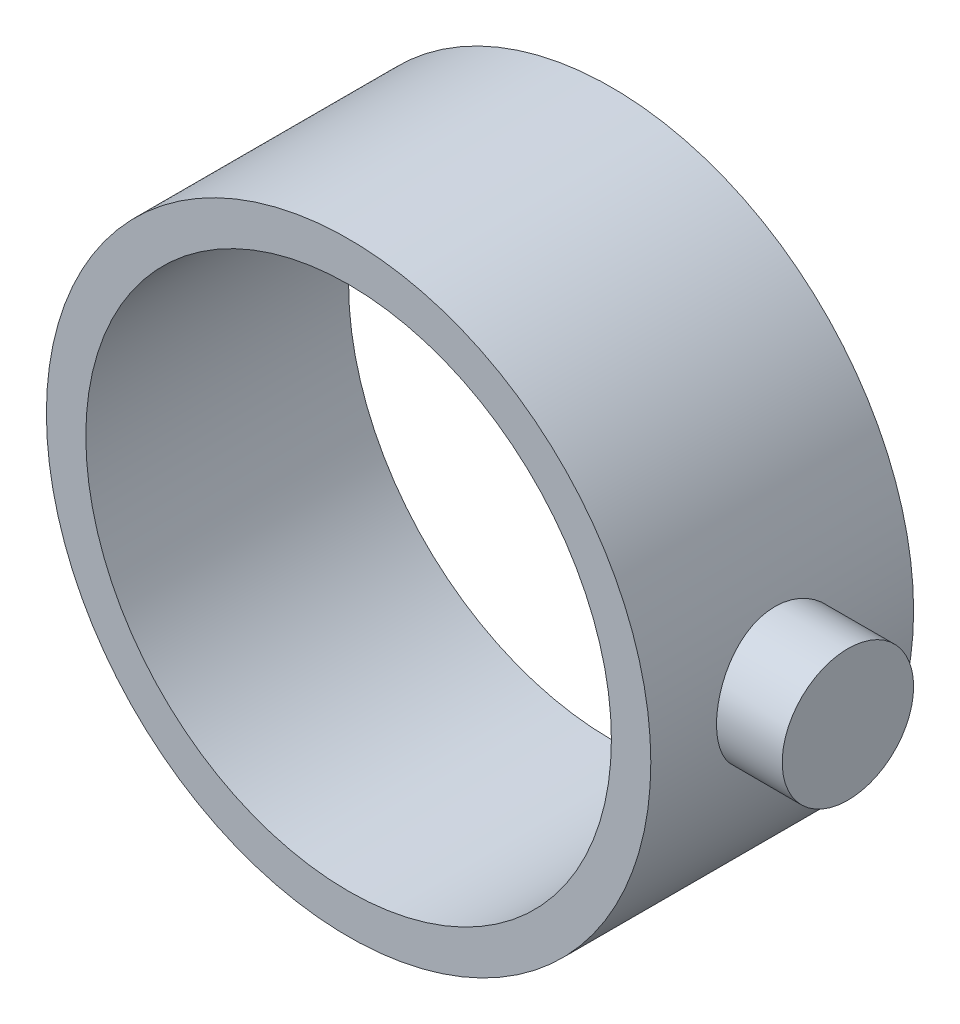
SolidWorks part; units mm, degrees
ref_plane "Front" through (0, 0, 0) normal (0, 0, 1) x (1, 0, 0)
ref_plane "Top" through (0, 0, 0) normal (0, 1, 0) x (1, 0, 0)
ref_plane "Right" through (0, 0, 0) normal (1, 0, 0) x (0, 0, -1)
sketch "Esquisse1" plane through (0, 0, 0) normal (0, 0, 1) x (1, 0, 0)
  circle A0 centre (0, 0) radius 20
  circle A1 centre (0, 0) radius 23
  dimension "D1" = 40
  dimension "D2" = 3
extrude "Boss.-Extru.1" add sketch "Esquisse1" along normal mid plane 20
ref_plane "Plan1" through (23, 0, 0) normal (1, 0, 0) x (0, 0, -1)
sketch "Esquisse2" plane through (23, 0, 0) normal (1, 0, 0) x (0, 0, -1)
  circle A0 centre (0, 0) radius 5
  dimension "D1" = 10
extrude "Boss.-Extru.2" add sketch "Esquisse2" against normal up to surface and the other way blind 5 up to face at (23, 0, 10)
sketch "Esquisse3" plane through (0, 0, 0) normal (0, 1, 0) x (1, 0, 0)
  line L0 (28, 0) -> (53, 0)
  line L1 (28, -5) -> (28, 5) construction
  line L2 (96.3013, 25) -> (133.8013, 89.9519)
  arc A0 (53, 0) -> (96.3013, 25) centre (53, 50) ccw
  arc A1 (133.8013, 89.9519) -> (155.4805, 110.035) centre (177.1025, 64.9519) cw
  dimension "D1" = 25
  dimension "D2" = 50
  dimension "D4" = 50
  dimension "D3" = 75
  dimension "D5" = 120
  dimension "D6" = 30
sketch "Esquisse4" plane through (28, 0, 0) normal (1, 0, 0) x (0, 0, -1)
  circle A0 centre (0, 0) radius 2.5
  dimension "D1" = 5
sweep "Balayage1" [suppressed] add profiles "Esquisse4" path "Esquisse3"
